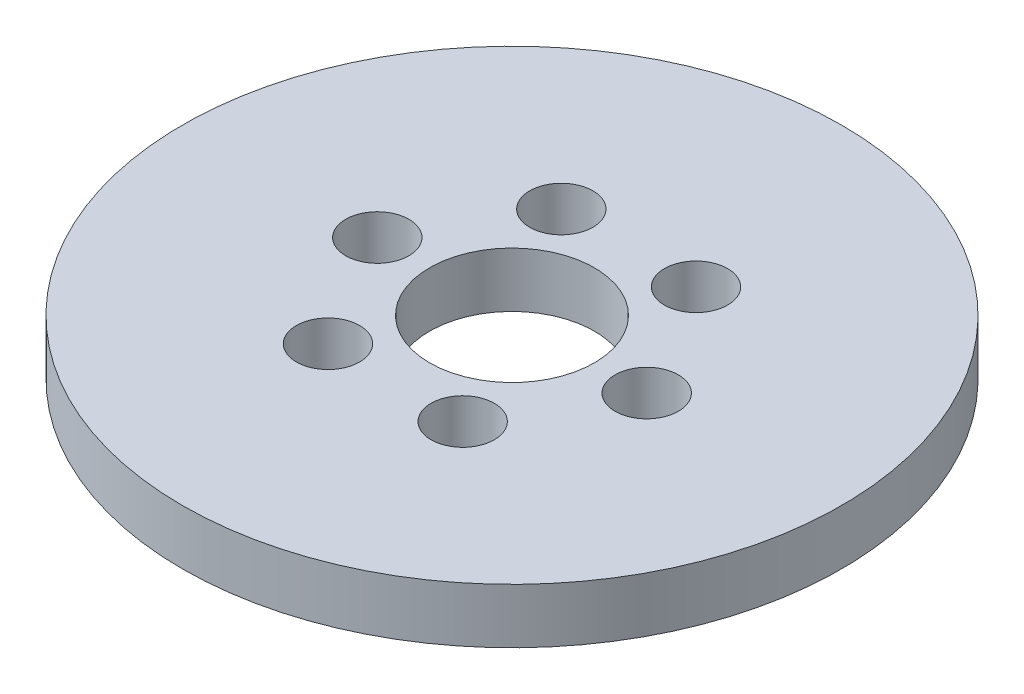
SolidWorks part; units mm, degrees
ref_plane "Front Plane" through (0, 0, 0) normal (0, 0, 1) x (1, 0, 0)
ref_plane "Top Plane" through (0, 0, 0) normal (0, 1, 0) x (1, 0, 0)
ref_plane "Right Plane" through (0, 0, 0) normal (1, 0, 0) x (0, 0, -1)
sketch "Sketch1" plane through (0, 0, 0) normal (0, 1, 0) x (1, 0, 0)
  circle A0 centre (0, 0) radius 60
  dimension "FLANGE_OD" = 120
extrude "Boss-Extrude1" add sketch "Sketch1" along normal blind 10
sketch "Sketch2" plane through (0, 0, 0) normal (0, 1, 0) x (1, 0, 0)
  circle A0 centre (0, 0) radius 15
  dimension "BORE_D" = 30
extrude "Cut-Extrude1" cut sketch "Sketch2" along normal through all
sketch "Sketch3" plane through (0, 10, 0) normal (0, 1, 0) x (1, 0, 0)
  circle A0 centre (0, 0) radius 24.5249 construction
  circle A1 centre (-24.5249, 0) radius 5.7577
  dimension "BOLT_D" = 11.5154
  dimension "BOLT_PCD" = 49.0499
extrude "Cut-Extrude2" cut sketch "Sketch3" against normal blind 8.7737
pattern_circular "CirPattern1" count 6 over 360 about axis through (0, 0, 0) along (0, 1, 0) of "Cut-Extrude2"
